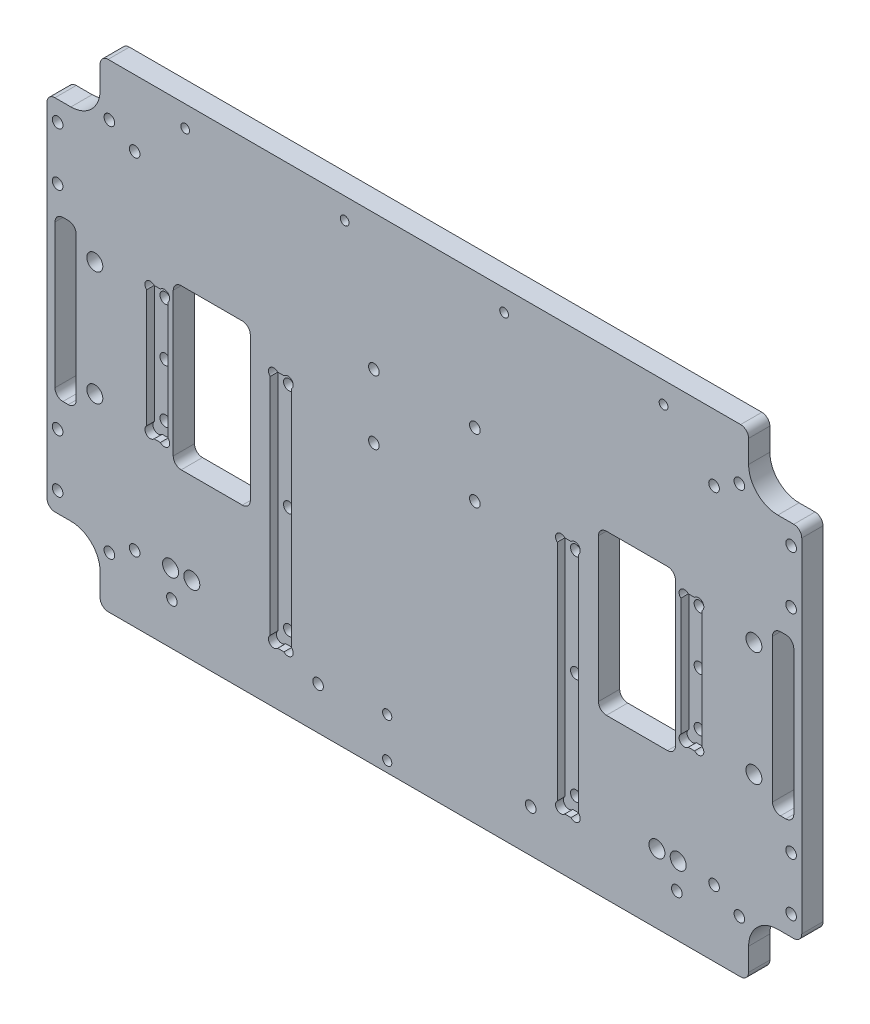
SolidWorks part; units mm, degrees
ref_plane "Front" through (0, 0, 0) normal (0, 0, 1) x (1, 0, 0)
ref_plane "Top" through (0, 0, 0) normal (0, 1, 0) x (1, 0, 0)
ref_plane "Right" through (0, 0, 0) normal (1, 0, 0) x (0, 0, -1)
sketch "Esquisse1" plane through (0, 0, 0) normal (0, 0, 1) x (1, 0, 0)
  line L1 (0, 0) -> (284, 0)
  line L2 (0, 0) -> (0, 180)
  line L3 (0, 180) -> (284, 180)
  line L4 (284, 0) -> (284, 180)
  dimension "D1" = 284
  dimension "D2" = 180
extrude "Boss.-Extru.1" add sketch "Esquisse1" along normal blind 8
sketch "Esquisse2" plane through (0, 0, 8) normal (0, 0, 1) x (1, 0, 0)
  line L0 (142, 180) -> (142, 0) construction
  line L1 (47.5, 60) -> (76.5, 60)
  line L2 (47.5, 60) -> (47.5, 120)
  line L3 (47.5, 120) -> (76.5, 120)
  line L4 (76.5, 60) -> (76.5, 120)
  line L5 (284, 180) -> (0, 180) construction
  line L6 (0, 0) -> (284, 0) construction
  line L7 (76.5, 90) -> (142, 90) construction
  line L8 (62, 60) -> (62, 120) construction
  line L9 (47.5, 90) -> (11, 90) construction
  line L10 (7, 60) -> (7, 120) construction
  line L11 (3, 60) -> (11, 60)
  line L12 (3, 60) -> (3, 120)
  line L13 (3, 120) -> (11, 120)
  line L14 (11, 60) -> (11, 120)
  line L15 (277, 60) -> (277, 120) construction
  line L16 (236.5, 90) -> (273, 90) construction
  line L17 (222, 60) -> (222, 120) construction
  line L18 (273, 60) -> (273, 120)
  line L19 (281, 120) -> (273, 120)
  line L20 (281, 60) -> (281, 120)
  line L21 (281, 60) -> (273, 60)
  line L22 (207.5, 60) -> (207.5, 120)
  line L23 (236.5, 120) -> (207.5, 120)
  line L24 (236.5, 60) -> (236.5, 120)
  line L25 (236.5, 60) -> (207.5, 60)
  dimension "D1" = 90
  dimension "D2" = 60
  dimension "D3" = 29
  dimension "D4" = 160
  dimension "D5" = 8
  dimension "D6" = 60
  dimension "D7" = 270
extrude "Enlèv. mat.-Extru.1" cut sketch "Esquisse2" against normal through all
sketch "Esquisse3" plane through (0, 0, 8) normal (0, 0, 1) x (1, 0, 0)
  line L0 (0, 172) -> (284, 172) construction
  line L1 (0, 180) -> (0, 0) construction
  line L2 (284, 0) -> (284, 180) construction
  line L3 (112, 172) -> (112, 180.3897) construction
  line L5 (172, 172) -> (172, 180.3897) construction
  line L6 (172, 180.3897) -> (112, 180.3897) construction
  line L7 (142, 180.3897) -> (142, 180) construction
  line L8 (284, 180) -> (0, 180) construction
  circle A0 centre (112, 172) radius 1.65
  circle A1 centre (172, 172) radius 1.65
  circle A2 centre (232, 172) radius 1.65
  circle A4 centre (52, 172) radius 1.65
  dimension "D1" = 3.3
  dimension "D2" = 4
  dimension "D3" = 8
  dimension "D4" = 60
extrude "Enlèv. mat.-Extru.2" cut sketch "Esquisse3" against normal up to vertex (8 mm away) up to point (284, 180, 0)
sketch "Esquisse4" plane through (0, 0, 8) normal (0, 0, 1) x (1, 0, 0)
  line L0 (142, 0) -> (142, 180) construction
  line L1 (84, 110) -> (92, 110)
  line L2 (84, 110) -> (84, 20)
  line L3 (84, 20) -> (92, 20)
  line L4 (92, 110) -> (92, 20)
  line L5 (0, 0) -> (284, 0) construction
  line L6 (284, 180) -> (0, 180) construction
  line L8 (76.5, 60) -> (76.5, 120) construction
  line L9 (192, 110) -> (192, 20)
  line L10 (200, 20) -> (192, 20)
  line L11 (200, 110) -> (200, 20)
  line L12 (200, 110) -> (192, 110)
  line L13 (47.5, 120) -> (47.5, 60) construction
  line L14 (37.5, 115) -> (45.5, 115)
  line L15 (37.5, 115) -> (37.5, 65)
  line L16 (37.5, 65) -> (45.5, 65)
  line L17 (45.5, 115) -> (45.5, 65)
  line L18 (45.5, 90) -> (47.5, 90) construction
  line L19 (238.5, 90) -> (236.5, 90) construction
  line L20 (238.5, 115) -> (238.5, 65)
  line L21 (246.5, 65) -> (238.5, 65)
  line L22 (246.5, 115) -> (246.5, 65)
  line L23 (246.5, 115) -> (238.5, 115)
  line L24 (47.5, 60) -> (76.5, 60) construction
  dimension "D1" = 40
  dimension "D2" = 90
  dimension "D3" = 8
  dimension "D4" = 7.5
  dimension "D5" = 8
  dimension "D6" = 2
  dimension "D7" = 50
extrude "Enlèv. mat.-Extru.3" cut sketch "Esquisse4" against normal blind 3
sketch "Esquisse5" plane through (0, 0, 8) normal (0, 0, 1) x (1, 0, 0)
  line L0 (142, 0) -> (142, 124.0722) construction
  line L2 (142, 117) -> (121.1311, 117) construction
  line L3 (0, 180) -> (0, 0) construction
  circle A0 centre (123, 129) radius 2
  circle A1 centre (123, 105) radius 2
  circle A2 centre (161, 105) radius 2
  circle A3 centre (161, 129) radius 2
  circle A5 centre (112, 172) radius 1.65 construction
  dimension "D1" = 38
  dimension "D2" = 4
  dimension "D3" = 24
  dimension "D4" = 55
  dimension "D5" = 142
extrude "Enlèv. mat.-Extru.4" cut sketch "Esquisse5" against normal through all
sketch "Esquisse6" plane through (0, 0, 8) normal (0, 0, 1) x (1, 0, 0)
  line L0 (142, 0) -> (142, 119.0936) construction
  line L1 (0, 0) -> (284, 0) construction
  line L2 (11, 90) -> (29.8915, 90) construction
  line L4 (11, 60) -> (11, 120) construction
  line L5 (273, 90) -> (254.1085, 90) construction
  circle A0 centre (18, 111.5) radius 3
  circle A1 centre (18, 68.5) radius 3
  circle A2 centre (266, 68.5) radius 3
  circle A3 centre (266, 111.5) radius 3
  dimension "D3" = 6
  dimension "D1" = 21.5
  dimension "D2" = 7
extrude "Enlèv. mat.-Extru.5" cut sketch "Esquisse6" against normal through all
sketch "Esquisse8" plane through (0, 0, 8) normal (0, 0, 1) x (1, 0, 0)
  line L0 (142, 180) -> (142, 109.7669) construction
  line L1 (0, 180) -> (20, 180)
  line L2 (0, 180) -> (0, 157.5)
  line L3 (0, 157.5) -> (20, 157.5)
  line L4 (20, 180) -> (20, 157.5)
  line L5 (284, 180) -> (0, 180) construction
  line L6 (264, 180) -> (264, 157.5)
  line L7 (284, 157.5) -> (264, 157.5)
  line L8 (284, 180) -> (284, 157.5)
  line L9 (284, 180) -> (264, 180)
  line L10 (264, 0) -> (264, 22.5)
  line L11 (0, 0) -> (20, 0)
  line L12 (0, 0) -> (0, 22.5)
  line L13 (0, 22.5) -> (20, 22.5)
  line L14 (20, 0) -> (20, 22.5)
  line L15 (284, 22.5) -> (264, 22.5)
  line L16 (284, 0) -> (284, 22.5)
  line L17 (284, 0) -> (264, 0)
  dimension "D1" = 22.5
  dimension "D2" = 20
  dimension "D3" = 22.5
extrude "Enlèv. mat.-Extru.7" cut sketch "Esquisse8" against normal through all
fillet "Congé1" radius 11 4 edges at (20, 157.5, 4) (264, 157.5, 4) (264, 22.5, 4) (20, 22.5, 4)
sketch "Esquisse7" plane through (0, 0, 8) normal (0, 0, 1) x (1, 0, 0)
  line L0 (142, 180) -> (142, 7.3256) construction
  line L1 (264, 180) -> (20, 180) construction
  line L2 (23.4737, 160.5) -> (33, 155) construction
  line L3 (264, 180) -> (20, 180) construction
  line L4 (260.5263, 160.5) -> (251, 155) construction
  line L5 (33, 155) -> (33, 25) construction
  line L6 (33, 90) -> (100.6533, 90) construction
  line L7 (23.4737, 19.5) -> (33, 25) construction
  line L8 (20, 0) -> (264, 0) construction
  line L9 (260.5263, 19.5) -> (251, 25) construction
  circle A0 centre (33, 155) radius 2
  circle A1 centre (23.4737, 160.5) radius 2
  circle A2 centre (260.5263, 160.5) radius 2
  circle A3 centre (251, 155) radius 2
  circle A5 centre (23.4737, 19.5) radius 2
  circle A6 centre (33, 25) radius 2
  circle A7 centre (251, 25) radius 2
  circle A8 centre (260.5263, 19.5) radius 2
  dimension "D1" = 4
  dimension "D5" = 25
  dimension "D2" = 11
  dimension "D3" = 109
  dimension "D4" = 30
  dimension "D6" = 25
extrude "Enlèv. mat.-Extru.6" cut sketch "Esquisse7" against normal through all
fillet "Congé2" radius 3 16 edges at (281, 60, 4) (273, 60, 4) (281, 120, 4) (273, 120, 4) (236.5, 120, 4) (207.5, 120, 4) (236.5, 60, 4) (207.5, 60, 4) (76.5, 60, 4) (47.5, 60, 4) (76.5, 120, 4) (47.5, 120, 4) (11, 120, 4) (3, 120, 4) (3, 60, 4) (11, 60, 4)
sketch "Esquisse9" plane through (0, 0, 8) normal (0, 0, 1) x (1, 0, 0)
  line L0 (37.5, 115) -> (38.8435, 113.6565) construction
  line L1 (45.5, 115) -> (37.5, 115) construction
  line L2 (41.5, 115) -> (41.5, 118.2808) construction
  line L3 (45.5, 115) -> (37.5, 115) construction
  line L4 (45.5, 115) -> (44.1565, 113.6565) construction
  line L5 (45.5, 90) -> (42.8729, 90) construction
  line L6 (45.5, 65) -> (45.5, 115) construction
  line L7 (45.5, 65) -> (44.1565, 66.3435) construction
  line L8 (37.5, 65) -> (38.8435, 66.3435) construction
  line L9 (45.5, 90) -> (238.5, 90) construction
  line L10 (238.5, 115) -> (238.5, 65) construction
  line L11 (142, 90) -> (142, 121.5895) construction
  line L12 (246.5, 65) -> (245.1565, 66.3435) construction
  line L13 (238.5, 65) -> (239.8435, 66.3435) construction
  line L14 (238.5, 90) -> (241.1271, 90) construction
  line L15 (238.5, 115) -> (239.8435, 113.6565) construction
  line L16 (242.5, 115) -> (242.5, 118.2808) construction
  line L17 (246.5, 115) -> (245.1565, 113.6565) construction
  line L18 (84, 110) -> (85.3435, 108.6565) construction
  line L19 (92, 110) -> (84, 110) construction
  line L20 (88, 110) -> (88, 112.2434) construction
  line L21 (92, 110) -> (84, 110) construction
  line L22 (92, 110) -> (90.6565, 108.6565) construction
  line L23 (84, 65) -> (89.3356, 65) construction
  line L24 (84, 110) -> (84, 20) construction
  line L25 (92, 20) -> (90.6565, 21.3435) construction
  line L26 (88, 20) -> (88, 17.7566) construction
  line L27 (84, 20) -> (85.3435, 21.3435) construction
  line L28 (200, 20) -> (198.6565, 21.3435) construction
  line L29 (196, 20) -> (196, 17.7566) construction
  line L30 (192, 20) -> (193.3435, 21.3435) construction
  line L31 (200, 65) -> (194.6644, 65) construction
  line L32 (192, 110) -> (193.3435, 108.6565) construction
  line L33 (196, 110) -> (196, 112.2434) construction
  line L34 (200, 110) -> (198.6565, 108.6565) construction
  circle A0 centre (38.8435, 113.6565) radius 2
  circle A1 centre (44.1565, 113.6565) radius 2
  circle A2 centre (44.1565, 66.3435) radius 2
  circle A3 centre (38.8435, 66.3435) radius 2
  circle A4 centre (245.1565, 66.3435) radius 2
  circle A5 centre (239.8435, 66.3435) radius 2
  circle A6 centre (239.8435, 113.6565) radius 2
  circle A7 centre (245.1565, 113.6565) radius 2
  circle A8 centre (85.3435, 108.6565) radius 2
  circle A9 centre (90.6565, 108.6565) radius 2
  circle A10 centre (90.6565, 21.3435) radius 2
  circle A11 centre (85.3435, 21.3435) radius 2
  circle A12 centre (198.6565, 21.3435) radius 2
  circle A13 centre (193.3435, 21.3435) radius 2
  circle A14 centre (193.3435, 108.6565) radius 2
  circle A15 centre (198.6565, 108.6565) radius 2
  dimension "D1" = 4
  dimension "D6" = 4
  dimension "D2" = 45
  dimension "D3" = 1.9
  dimension "D4" = 45
  dimension "D5" = 1.9
extrude "Enlèv. mat.-Extru.8" cut sketch "Esquisse9" against normal up to vertex (3 mm away) up to point (37.5, 65, 5)
fillet "Congé3" radius 3 8 edges at (264, 180, 4) (284, 157.5, 4) (284, 22.5, 4) (264, 0, 4) (20, 0, 4) (0, 22.5, 4) (0, 157.5, 4) (20, 180, 4)
sketch "Esquisse10" plane through (0, 0, 5) normal (0, 0, 1) x (1, 0, 0)
  line L0 (41.5, 115) -> (41.5, 65) construction
  line L1 (42.6749, 115) -> (40.3251, 115) construction
  line L2 (40.3251, 65) -> (42.6749, 65) construction
  line L3 (41.5, 90) -> (37.5, 90) construction
  line L4 (37.5, 112.1749) -> (37.5, 67.8251) construction
  line L5 (88, 110) -> (88, 20) construction
  line L6 (89.1749, 110) -> (86.8251, 110) construction
  line L7 (86.8251, 20) -> (89.1749, 20) construction
  line L8 (88, 65) -> (84, 65) construction
  line L9 (84, 107.1749) -> (84, 22.8251) construction
  line L10 (142, 0) -> (142, 180) construction
  line L11 (23, 0) -> (261, 0) construction
  line L12 (261, 180) -> (23, 180) construction
  line L13 (196, 65) -> (200, 65) construction
  line L14 (196, 110) -> (196, 20) construction
  line L15 (242.5, 90) -> (246.5, 90) construction
  line L16 (242.5, 115) -> (242.5, 65) construction
  circle A0 centre (41.5, 90) radius 2
  circle A1 centre (41.5, 70) radius 2
  circle A2 centre (41.5, 110) radius 2
  circle A3 centre (88, 65) radius 2
  circle A4 centre (88, 25) radius 2
  circle A5 centre (88, 105) radius 2
  circle A6 centre (196, 105) radius 2
  circle A7 centre (196, 25) radius 2
  circle A8 centre (196, 65) radius 2
  circle A9 centre (242.5, 110) radius 2
  circle A10 centre (242.5, 70) radius 2
  circle A11 centre (242.5, 90) radius 2
  dimension "D1" = 4
  dimension "D2" = 20
  dimension "D3" = 40
extrude "Enlèv. mat.-Extru.9" cut sketch "Esquisse10" against normal through all
sketch "Esquisse11" plane through (0, 0, 8) normal (0, 0, 1) x (1, 0, 0)
  line L0 (142, 0) -> (142, 52.4414) construction
  line L1 (23, 0) -> (261, 0) construction
  line L2 (142, 16) -> (47, 16) construction
  line L3 (86.8251, 20) -> (89.1749, 20) construction
  line L4 (46.5, 26) -> (54.5, 26) construction
  line L5 (237.5, 26) -> (229.5, 26) construction
  circle A0 centre (47, 16) radius 2
  circle A1 centre (237, 16) radius 2
  circle A2 centre (102, 16) radius 2
  circle A3 centre (46.5, 26) radius 3
  circle A4 centre (54.5, 26) radius 3
  circle A5 centre (229.5, 26) radius 3
  circle A6 centre (237.5, 26) radius 3
  circle A7 centre (182, 16) radius 2
  point P10 (94.5, 16)
  point P13 (88, 20)
  dimension "D1" = 4
  dimension "D2" = 190
  dimension "D4" = 8
  dimension "D5" = 10
  dimension "D7" = 6
  dimension "D8" = 80
  dimension "D3" = 4
  dimension "D6" = 87.5
extrude "Enlèv. mat.-Extru.10" cut sketch "Esquisse11" against normal through all
sketch "Esquisse12" plane through (0, 0, 8) normal (0, 0, 1) x (1, 0, 0)
  line L0 (128, 0) -> (128, 19) construction
  line L1 (23, 0) -> (261, 0) construction
  circle A0 centre (128, 4) radius 1.75
  circle A1 centre (128, 19) radius 1.75
  dimension "D1" = 15
  dimension "D2" = 3.5
  dimension "D3" = 4
  dimension "D4" = 128
extrude "Enlèv. mat.-Extru.11" cut sketch "Esquisse12" against normal through all
sketch "Esquisse13" plane through (0, 0, 8) normal (0, 0, 1) x (1, 0, 0)
  line L0 (4, 157.5) -> (4, 22.5) construction
  line L1 (3, 157.5) -> (9, 157.5) construction
  line L2 (9, 22.5) -> (3, 22.5) construction
  line L3 (0, 154.5) -> (0, 25.5) construction
  line L4 (11, 90) -> (4, 90) construction
  line L5 (11, 63) -> (11, 117) construction
  line L6 (142, 0) -> (142, 180) construction
  line L7 (23, 0) -> (261, 0) construction
  line L8 (261, 180) -> (23, 180) construction
  line L9 (273, 90) -> (280, 90) construction
  line L10 (280, 157.5) -> (280, 22.5) construction
  circle A0 centre (4, 30) radius 2
  circle A1 centre (4, 50) radius 2
  circle A2 centre (4, 130) radius 2
  circle A3 centre (4, 150) radius 2
  circle A4 centre (280, 150) radius 2
  circle A5 centre (280, 130) radius 2
  circle A6 centre (280, 50) radius 2
  circle A7 centre (280, 30) radius 2
  dimension "D2" = 20
  dimension "D3" = 4
  dimension "D4" = 80
  dimension "D1" = 4
extrude "Enlèv. mat.-Extru.12" cut sketch "Esquisse13" against normal through all
